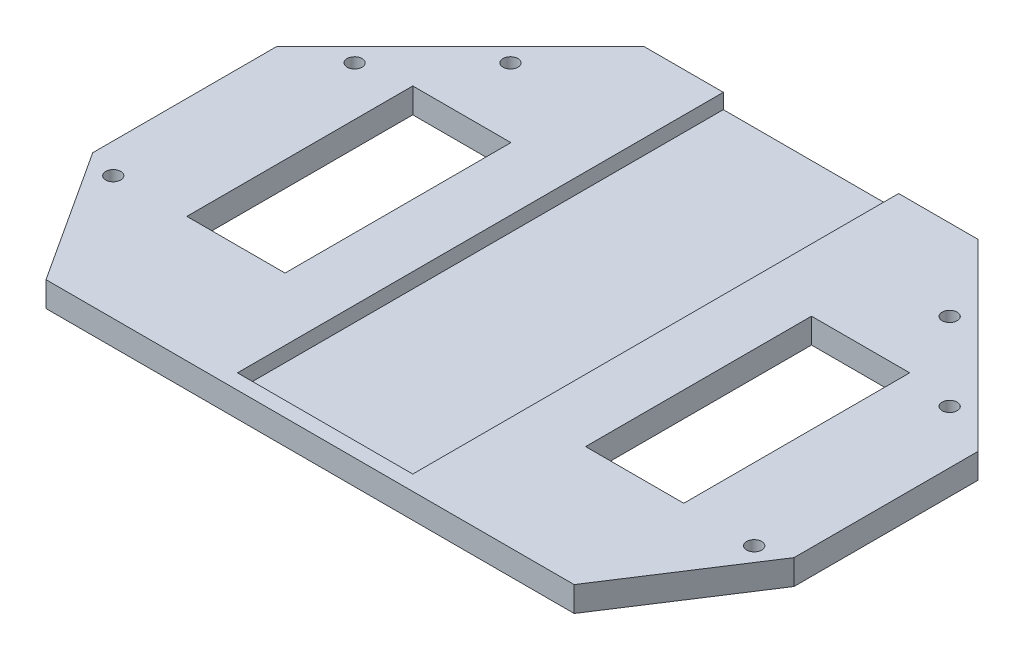
SolidWorks part; units mm, degrees
ref_plane "Front Plane" through (0, 0, 0) normal (0, 0, 1) x (1, 0, 0)
ref_plane "Top Plane" through (0, 0, 0) normal (0, 1, 0) x (1, 0, 0)
ref_plane "Right Plane" through (0, 0, 0) normal (1, 0, 0) x (0, 0, -1)
sketch "Sketch1" plane through (0, 0, 0) normal (0, 1, 0) x (1, 0, 0)
  line L0 (-52.7197, -40) -> (-70, -13.3906)
  line L1 (-70, -13.3906) -> (-70, 23.3381)
  line L2 (-70, 23.3381) -> (-33.3381, 60)
  line L4 (0, -40) -> (0, 60)
  line L5 (0, -40) -> (-52.7197, -40)
  line L6 (-59.397, 28.2843) -> (-43.8406, 43.8406) construction
  line L7 (-51.9976, -33.7676) -> (-63.9796, -15.3169) construction
  line L8 (-33.3381, 60) -> (0, 60)
  line L9 (0, 0) -> (-85, 0) construction
  line L10 (-43.8406, 43.8406) -> (0, 0) construction
  line L11 (-51.9976, -33.7676) -> (0, 0) construction
  line L12 (-49.6, 30.1) -> (-30, 30.1)
  line L13 (-49.6, 30.1) -> (-49.6, -15)
  line L14 (-49.6, -15) -> (-30, -15)
  line L15 (-30, 30.1) -> (-30, -15)
  circle A0 centre (0, 0) radius 85 construction
  circle A1 centre (-43.8406, 43.8406) radius 1.5
  circle A2 centre (-59.397, 28.2843) radius 1.5
  circle A4 centre (-63.9796, -15.3169) radius 1.5
  dimension "D7" = 3
  dimension "D17" = 170
  dimension "D2" = 60
  dimension "D3" = 4
  dimension "D5" = 40
  dimension "D6" = 70
  dimension "D8" = 62
  dimension "D9" = 22
  dimension "D10" = 22
  dimension "D11" = 19.6
  dimension "D12" = 45.1
  dimension "D13" = 30
  dimension "D14" = 45
  dimension "D15" = 33
  dimension "D16" = 15
  dimension "D18" = 4
extrude "Boss-Extrude1" add sketch "Sketch1" along normal blind 5
mirror "Mirror1" about plane through (0, 5, 40) normal (-1, 0, 0) of "Boss-Extrude1"
sketch "Sketch2" plane through (0, 5, 0) normal (0, 1, 0) x (1, 0, 0)
  line L0 (33.3381, 60) -> (-33.3381, 60) construction
  line L1 (-17.5, 60) -> (17.5, 60)
  line L2 (-17.5, 60) -> (-17.5, -37)
  line L3 (-17.5, -37) -> (17.5, -37)
  line L4 (17.5, 60) -> (17.5, -37)
  line L5 (-52.7197, -40) -> (52.7197, -40) construction
  dimension "D1" = 3
  dimension "D2" = 35
  dimension "D3" = 17.5
extrude "Cut-Extrude1" cut sketch "Sketch2" against normal blind 3
